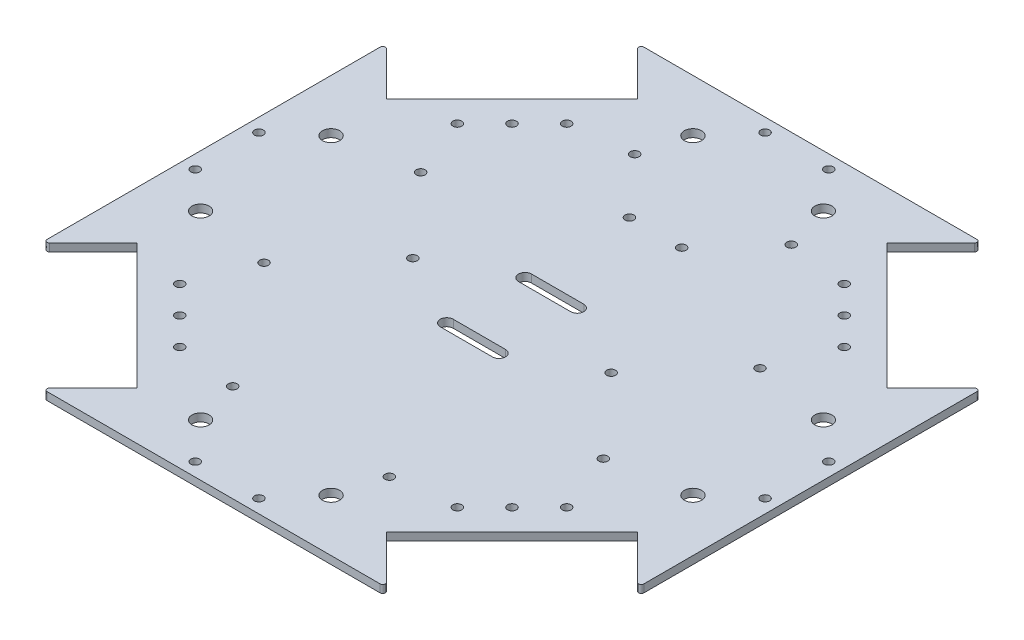
SolidWorks part; units mm, degrees
ref_plane "Front Plane" through (0, 0, 0) normal (0, 0, 1) x (1, 0, 0)
ref_plane "Top Plane" through (0, 0, 0) normal (0, 1, 0) x (1, 0, 0)
ref_plane "Right Plane" through (0, 0, 0) normal (1, 0, 0) x (0, 0, -1)
sketch "Sketch1" plane through (0, 0, 0) normal (0, 1, 0) x (1, 0, 0)
  line L1 (-114.3, 114.3) -> (114.3, 114.3)
  line L2 (-114.3, 114.3) -> (-114.3, -114.3)
  line L3 (-114.3, -114.3) -> (114.3, -114.3)
  line L4 (114.3, 114.3) -> (114.3, -114.3)
  line L5 (-114.3, 114.3) -> (114.3, -114.3) construction
  line L6 (-114.3, -114.3) -> (114.3, 114.3) construction
  point P0 (0, 0)
  dimension "D1" = 228.6
  dimension "D2" = 228.6
extrude "plate" add sketch "Sketch1" along normal blind 3
sketch "Sketch8" plane through (0, 3, 0) normal (0, 1, 0) x (1, 0, 0)
  line L0 (-114.3, 114.3) -> (114.3, -114.3) construction
  line L1 (114.3, 114.3) -> (-114.3, -114.3) construction
  line L2 (-50.6604, 177.9396) -> (177.9396, -50.6604) construction
  line L3 (0, 0) -> (63.6396, 63.6396) construction
  circle A0 centre (63.6396, 63.6396) radius 1.7
  circle A1 centre (74.1048, 53.1744) radius 1.7
  circle A2 centre (53.1744, 74.1048) radius 1.7
  circle A3 centre (63.6396, -63.6396) radius 1.7
  circle A4 centre (74.1048, -53.1744) radius 1.7
  circle A5 centre (53.1744, -74.1048) radius 1.7
  circle A6 centre (-63.6396, -63.6396) radius 1.7
  circle A7 centre (-53.1744, -74.1048) radius 1.7
  circle A8 centre (-74.1048, -53.1744) radius 1.7
  circle A9 centre (-63.6396, 63.6396) radius 1.7
  circle A10 centre (-74.1048, 53.1744) radius 1.7
  circle A11 centre (-53.1744, 74.1048) radius 1.7
  dimension "D2" = 3.4
  dimension "D3" = 3.4
  dimension "D4" = 3.4
  dimension "D5" = 14.8
  dimension "D6" = 14.8
  dimension "D8" = 90
  dimension "D9" = 90
  dimension "D1" = 90
  dimension "D7" = 4
extrude "motor-mount-holes" cut sketch "Sketch8" against normal blind 3
sketch "Sketch9" plane through (0, 3, 0) normal (0, 1, 0) x (1, 0, 0)
  line L0 (0, -114.3) -> (0, 114.3) construction
  line L1 (-38, 0) -> (38, 0) construction
  line L4 (114.3, 114.3) -> (-114.3, 114.3) construction
  line L5 (-114.3, -114.3) -> (114.3, -114.3) construction
  circle A0 centre (-38, 0) radius 1.7
  circle A1 centre (38, 0) radius 1.7
  point P3 (0, 0)
  dimension "D3" = 3.4
  dimension "D2" = 38
extrude "connector-board-holes" cut sketch "Sketch9" against normal blind 3
sketch "Sketch11" plane through (0, 3, 0) normal (0, 1, 0) x (1, 0, 0)
  line L0 (-114.3, 0) -> (114.3, 0) construction
  line L1 (-114.3, 55) -> (114.3, 55) construction
  line L2 (0, -114.3) -> (0, 114.3) construction
  line L3 (27.5, -114.3) -> (27.5, 114.3) construction
  line L4 (-27.5, -114.3) -> (-27.5, 114.3) construction
  line L5 (-123.5172, 0) -> (114.3, 0) construction
  line L6 (-114.3, 114.3) -> (-114.3, -114.3) construction
  line L7 (114.3, -114.3) -> (114.3, 114.3) construction
  line L8 (0, -94.2235) -> (0, 114.3) construction
  line L9 (114.3, 114.3) -> (-114.3, 114.3) construction
  line L10 (-114.3, -114.3) -> (114.3, -114.3) construction
  line L11 (-123.5172, 55) -> (114.3, 55) construction
  line L12 (-27.5, -94.2235) -> (-27.5, 114.3) construction
  line L13 (27.5, -94.2235) -> (27.5, 114.3) construction
  circle A0 centre (-10, 55) radius 1.7
  circle A1 centre (10, 55) radius 1.7
  dimension "D4" = 3.4
  dimension "D5" = 3.4
  dimension "D6" = 10
  dimension "D7" = 20
  dimension "D1" = 55
  dimension "D2" = 27.5
  dimension "D3" = 27.5
extrude "motor-controller-holder-arduino-holes" cut sketch "Sketch11" against normal up to next
sketch "Sketch12" plane through (0, 3, 0) normal (0, 1, 0) x (1, 0, 0)
  line L0 (114.3, 0) -> (-114.3, 0) construction
  line L1 (114.3, -114.3) -> (114.3, 114.3) construction
  line L2 (-114.3, 114.3) -> (-114.3, -114.3) construction
  line L3 (-10, 15) -> (10, 15) construction
  line L4 (-10, 17.5) -> (10, 17.5)
  line L5 (-10, 12.5) -> (10, 12.5)
  line L6 (-10, -15) -> (10, -15) construction
  line L7 (-10, -12.5) -> (10, -12.5)
  line L8 (-10, -17.5) -> (10, -17.5)
  line L9 (0, 114.3) -> (0, -114.3) construction
  line L10 (114.3, 114.3) -> (-114.3, 114.3) construction
  line L11 (-114.3, -114.3) -> (114.3, -114.3) construction
  arc A0 (-10, 17.5) -> (-10, 12.5) centre (-10, 15) ccw
  arc A1 (10, 12.5) -> (10, 17.5) centre (10, 15) ccw
  arc A2 (-10, -12.5) -> (-10, -17.5) centre (-10, -15) ccw
  arc A3 (10, -17.5) -> (10, -12.5) centre (10, -15) ccw
  point P8 (0, 15)
  point P13 (0, -15)
  dimension "D5" = 2.5
  dimension "D6" = 2.5
  dimension "D1" = 15
  dimension "D2" = 15
  dimension "D3" = 20
  dimension "D4" = 20
extrude "cable-slots" cut sketch "Sketch12" against normal up to next
sketch "Sketch13" plane through (0, 3, 0) normal (0, 1, 0) x (1, 0, 0)
  line L0 (0, -114.3) -> (0, 114.3) construction
  line L1 (-114.3, -114.3) -> (114.3, -114.3) construction
  line L2 (114.3, 114.3) -> (-114.3, 114.3) construction
  line L3 (-114.3, 109.1438) -> (114.3, 109.1438) construction
  line L4 (-114.3, 114.3) -> (-114.3, -114.3) construction
  line L5 (114.3, -114.3) -> (114.3, 114.3) construction
  line L6 (0, 0) -> (12.2, 109.1438) construction
  circle A0 centre (-12.2, 109.1438) radius 1.7
  circle A1 centre (12.2, 109.1438) radius 1.7
  circle A14 centre (109.1438, -12.2) radius 1.7
  circle A15 centre (109.1438, 12.2) radius 1.7
  circle A16 centre (-12.2, -109.1438) radius 1.7
  circle A17 centre (12.2, -109.1438) radius 1.7
  circle A18 centre (-109.1438, 12.2) radius 1.7
  circle A19 centre (-109.1438, -12.2) radius 1.7
  dimension "D2" = 3.4
  dimension "D3" = 3.4
  dimension "D1" = 5.1562
  dimension "D4" = 12.2
  dimension "D5" = 12.2
  dimension "D7" = 109.8235
  dimension "D8" = 6.378
  dimension "D6" = 4
extrude "wall-bracket-holes" cut sketch "Sketch13" against normal up to next
sketch "Sketch14" plane through (0, 3, 0) normal (0, 1, 0) x (1, 0, 0)
  line L0 (-114.3, 0) -> (114.3, 0) construction
  line L1 (-114.3, 114.3) -> (-114.3, -114.3) construction
  line L2 (114.3, -114.3) -> (114.3, 114.3) construction
  line L4 (0, 114.3) -> (0, -114.3) construction
  line L5 (114.3, 114.3) -> (-114.3, 114.3) construction
  line L6 (-114.3, -114.3) -> (114.3, -114.3) construction
  line L7 (-65, 30) -> (-65, -30) construction
  circle A8 centre (-65, 30) radius 1.7
  circle A9 centre (-65, -30) radius 1.7
  circle A10 centre (65, -30) radius 1.7
  circle A11 centre (65, 30) radius 1.7
  point P26 (-65, 0)
  dimension "D6" = 3.4
  dimension "D7" = 30
  dimension "D8" = 65
extrude "battery-holder-holes" cut sketch "Sketch14" against normal up to next
sketch "Sketch15" plane through (0, 3, 0) normal (0, 1, 0) x (1, 0, 0)
  line L0 (114.3, 0) -> (-114.3, 0) construction
  line L1 (114.3, -114.3) -> (114.3, 114.3) construction
  line L2 (-114.3, 114.3) -> (-114.3, -114.3) construction
  line L3 (114.3, 114.3) -> (-114.3, 114.3) construction
  line L4 (-25, 94.3) -> (25, 94.3) construction
  line L5 (-25, -94.3) -> (25, -94.3) construction
  line L6 (-114.3, -114.3) -> (114.3, -114.3) construction
  line L8 (0, 94.3) -> (0, 114.3) construction
  circle A0 centre (-94.3, 25) radius 3.3
  circle A1 centre (-94.3, -25) radius 3.3
  circle A2 centre (94.3, 25) radius 3.3
  circle A3 centre (94.3, -25) radius 3.3
  circle A4 centre (25, 94.3) radius 3.3
  circle A5 centre (-25, 94.3) radius 3.3
  circle A6 centre (25, -94.3) radius 3.3
  circle A7 centre (-25, -94.3) radius 3.3
  point P25 (0, 0)
  dimension "D3" = 6.6
  dimension "D4" = 6.6
  dimension "D6" = 6.6
  dimension "D7" = 6.6
  dimension "D13" = 20
  dimension "D1" = 50
  dimension "D2" = 25
  dimension "D5" = 20
  dimension "D8" = 25
  dimension "D9" = 50
  dimension "D10" = 20
  dimension "D12" = 20
  dimension "D11" = 2
extrude "load-mount-holes" cut sketch "Sketch15" against normal up to next
sketch "Sketch10" plane through (0, 3, 0) normal (0, 1, 0) x (1, 0, 0)
  line L0 (0, 114.3) -> (0, -114.3) construction
  line L1 (114.3, 114.3) -> (-114.3, 114.3) construction
  line L2 (-114.3, -114.3) -> (114.3, -114.3) construction
  line L3 (-114.3, 0) -> (114.3, 0) construction
  line L4 (-114.3, 114.3) -> (-114.3, -114.3) construction
  line L5 (114.3, -114.3) -> (114.3, 114.3) construction
  line L6 (30, 77) -> (-30, 77) construction
  line L7 (-30, 77) -> (-30, -77) construction
  circle A5 centre (30, 77) radius 1.7
  circle A6 centre (30, -77) radius 1.7
  circle A7 centre (-30, -77) radius 1.7
  circle A8 centre (-30, 77) radius 1.7
  point P20 (0, 77)
  point P21 (-30, 0)
  dimension "D1" = 3.4
  dimension "D2" = 30
  dimension "D3" = 77
extrude "level2-standoff-holes" cut sketch "Sketch10" against normal up to next
sketch "Sketch2" plane through (0, 3, 0) normal (0, 1, 0) x (1, 0, 0)
  line L0 (-114.3, -114.3) -> (114.3, 114.3) construction
  line L1 (114.3, -114.3) -> (-114.3, 114.3) construction
  line L2 (-90.2584, -138.3416) -> (138.3416, 90.2584) construction
  line L3 (-138.3416, -90.2584) -> (90.2584, 138.3416) construction
  line L4 (186.142, -42.458) -> (-42.458, 186.142) construction
  line L5 (114.3, 114.3) -> (66.2167, 114.3)
  line L6 (114.3, 114.3) -> (-114.3, 114.3) construction
  line L7 (66.2167, 114.3) -> (47.8004, 95.8837)
  line L8 (47.8004, 95.8837) -> (95.8837, 47.8004)
  line L9 (95.8837, 47.8004) -> (114.3, 66.2167)
  line L10 (114.3, 66.2167) -> (114.3, 114.3)
  line L41 (66.2167, -114.3) -> (114.3, -114.3)
  line L42 (114.3, -114.3) -> (114.3, -66.2167)
  line L43 (114.3, -66.2167) -> (95.8837, -47.8004)
  line L44 (95.8837, -47.8004) -> (47.8004, -95.8837)
  line L45 (47.8004, -95.8837) -> (66.2167, -114.3)
  line L46 (-114.3, -66.2167) -> (-114.3, -114.3)
  line L47 (-114.3, -114.3) -> (-66.2167, -114.3)
  line L48 (-66.2167, -114.3) -> (-47.8004, -95.8837)
  line L49 (-47.8004, -95.8837) -> (-95.8837, -47.8004)
  line L50 (-95.8837, -47.8004) -> (-114.3, -66.2167)
  line L51 (-66.2167, 114.3) -> (-114.3, 114.3)
  line L52 (-114.3, 114.3) -> (-114.3, 66.2167)
  line L53 (-114.3, 66.2167) -> (-95.8837, 47.8004)
  line L54 (-95.8837, 47.8004) -> (-47.8004, 95.8837)
  line L55 (-47.8004, 95.8837) -> (-66.2167, 114.3)
  line L56 (0, 0) -> (95.8837, 47.8004) construction
  dimension "D5" = 107.138
  dimension "D6" = 18.503
  dimension "D1" = 34
  dimension "D2" = 34
  dimension "D3" = 101.6
  dimension "D4" = 4
extrude "wheel-slots" cut sketch "Sketch2" against normal blind 3
fillet "Fillet1" radius 1 8 edges at (66.2167, 1.5, -114.3) (114.3, 1.5, -66.2167) (114.3, 1.5, 66.2167) (-66.2167, 1.5, -114.3) (-114.3, 1.5, -66.2167) (-114.3, 1.5, 66.2167) (-66.2167, 1.5, 114.3) (66.2167, 1.5, 114.3)
